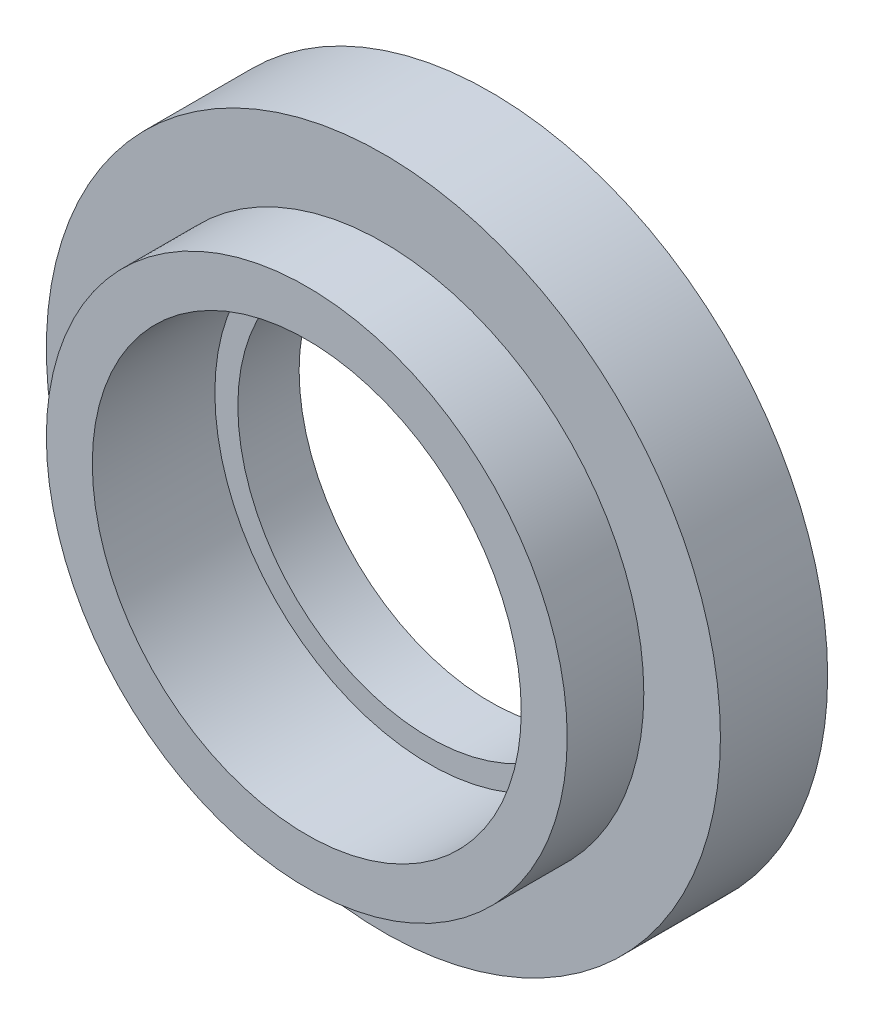
SolidWorks part; units mm, degrees
ref_plane "Front Plane" through (0, 0, 0) normal (0, 0, 1) x (1, 0, 0)
ref_plane "Top Plane" through (0, 0, 0) normal (0, 1, 0) x (1, 0, 0)
ref_plane "Right Plane" through (0, 0, 0) normal (1, 0, 0) x (0, 0, -1)
sketch "Sketch2" plane through (0, 0, 0) normal (0, 1, 0) x (1, 0, 0)
  line L0 (0, 0) -> (-22, 0)
  line L1 (-22, 0) -> (-22, -7)
  line L2 (-22, -7) -> (-17, -7)
  line L3 (-17, -7) -> (-17, -12)
  line L4 (-17, -12) -> (0, -12)
  line L5 (0, -12) -> (0, 0)
  dimension "D1" = 7
  dimension "D2" = 5
  dimension "D3" = 22
  dimension "D4" = 17
revolve "Revolve4" add sketch "Sketch2" angle 360 about L5
sketch "Sketch4" plane through (0, 0, 12) normal (0, 0, 1) x (1, 0, 0)
  circle A0 centre (0, 0) radius 14
  dimension "D1" = 28
extrude "Cut-Extrude1" cut sketch "Sketch4" against normal blind 8
sketch "Sketch5" plane through (0, 0, 0) normal (0, 0, -1) x (-1, 0, 0)
  circle A0 centre (0, 0) radius 12.5
  dimension "D1" = 25
extrude "Cut-Extrude4" cut sketch "Sketch5" against normal blind 8.1
sketch "Sketch7" plane through (0, 0, 0) normal (0, 0, -1) x (-1, 0, 0)
  circle A0 centre (0, 17) radius 2.5
  circle A2 centre (14.7224, 8.5) radius 2.5
  circle A3 centre (14.7224, -8.5) radius 2.5
  circle A4 centre (0, -17) radius 2.5
  circle A5 centre (-14.7224, -8.5) radius 2.5
  circle A6 centre (-14.7224, 8.5) radius 2.5
  point P15 (0, 0)
  dimension "D1" = 6
extrude "Cut-Extrude5" cut sketch "Sketch7" against normal blind 3
